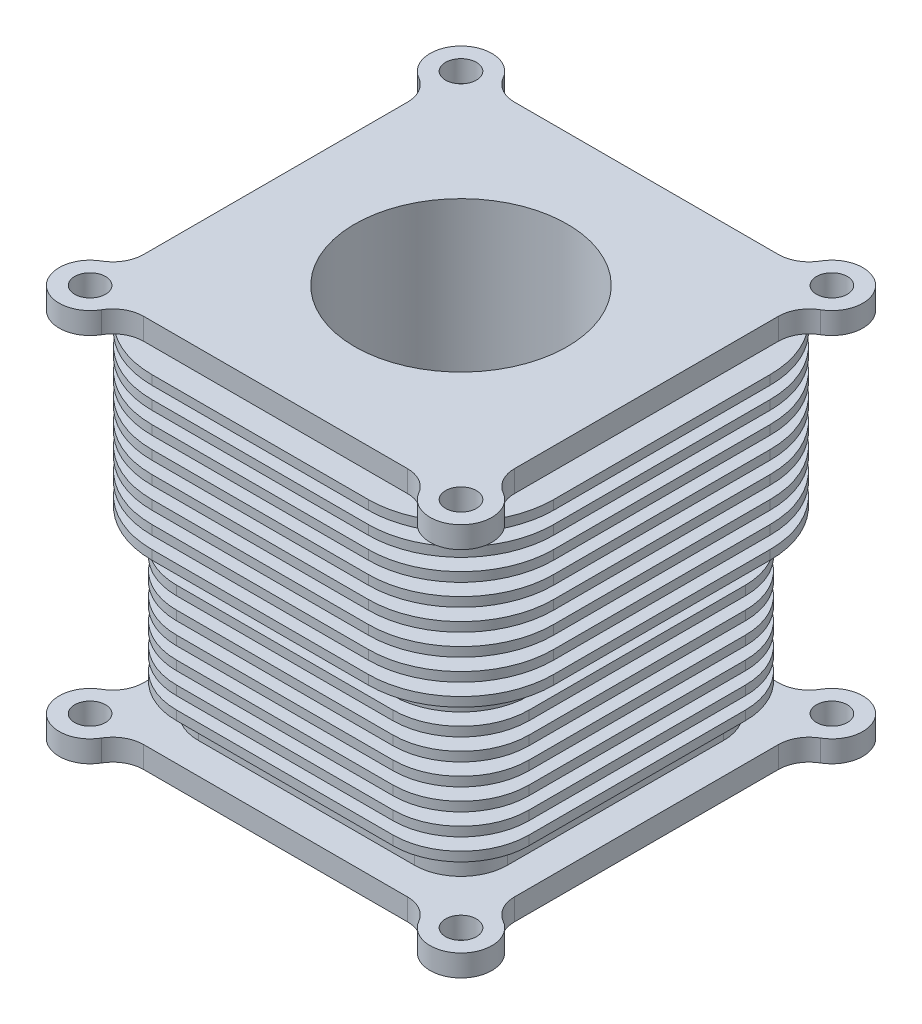
SolidWorks part; units mm, degrees
ref_plane "Front Plane" through (0, 0, 0) normal (0, 0, 1) x (1, 0, 0)
ref_plane "Top Plane" through (0, 0, 0) normal (0, 1, 0) x (1, 0, 0)
ref_plane "Right Plane" through (0, 0, 0) normal (1, 0, 0) x (0, 0, -1)
sketch "Sketch2" plane through (0, 0, 0) normal (0, 1, 0) x (1, 0, 0)
  line L1 (-63.5, 76.2) -> (63.5, 76.2)
  line L2 (-76.2, 63.5) -> (-76.2, -63.5)
  line L3 (-63.5, -76.2) -> (63.5, -76.2)
  line L4 (76.2, 63.5) -> (76.2, -63.5)
  line L5 (-76.2, 76.2) -> (76.2, -76.2) construction
  line L6 (-76.2, -76.2) -> (76.2, 76.2) construction
  arc A0 (-63.5, 76.2) -> (-76.2, 63.5) centre (-76.2, 76.2) ccw
  arc A1 (76.2, 63.5) -> (63.5, 76.2) centre (76.2, 76.2) ccw
  arc A2 (63.5, -76.2) -> (76.2, -63.5) centre (76.2, -76.2) ccw
  arc A3 (-76.2, -63.5) -> (-63.5, -76.2) centre (-76.2, -76.2) ccw
  point P0 (0, 0)
  dimension "D2" = 25.4
  dimension "D1" = 152.4
extrude "Boss-Extrude1" add sketch "Sketch2" along normal blind 8.89
fillet "Fillet1" radius 12.7 8 edges at (-63.5, 4.445, -76.2) (63.5, 4.445, -76.2) (76.2, 4.445, -63.5) (-76.2, 4.445, 63.5) (-76.2, 4.445, -63.5) (76.2, 4.445, 63.5) (63.5, 4.445, 76.2) (-63.5, 4.445, 76.2)
sketch "Sketch3" plane through (0, 8.89, 0) normal (0, 1, 0) x (1, 0, 0)
  line L1 (-63.5, 63.5) -> (63.5, 63.5)
  line L2 (-63.5, 63.5) -> (-63.5, -63.5)
  line L3 (-63.5, -63.5) -> (63.5, -63.5)
  line L4 (63.5, 63.5) -> (63.5, -63.5)
  line L5 (-63.5, 63.5) -> (63.5, -63.5) construction
  line L6 (-63.5, -63.5) -> (63.5, 63.5) construction
  point P0 (0, 0)
  dimension "D1" = 127
extrude "Boss-Extrude2" add sketch "Sketch3" along normal blind 152.4
fillet "Fillet2" radius 19.05 4 edges at (-63.5, 85.09, 63.5) (-63.5, 85.09, -63.5) (63.5, 85.09, -63.5) (63.5, 85.09, 63.5)
sketch "Sketch6" plane through (0, 161.29, 0) normal (0, 1, 0) x (1, 0, 0)
  line L8 (-82.55, 44.45) -> (-82.55, -44.45)
  line L9 (-44.45, -82.55) -> (44.45, -82.55)
  line L10 (82.55, -44.45) -> (82.55, 44.45)
  line L11 (44.45, 82.55) -> (-44.45, 82.55)
  line L12 (-82.55, 44.45) -> (-82.55, -44.45)
  line L13 (-44.45, -82.55) -> (44.45, -82.55)
  line L14 (82.55, -44.45) -> (82.55, 44.45)
  line L15 (44.45, 82.55) -> (-44.45, 82.55)
  arc A8 (-82.55, -44.45) -> (-44.45, -82.55) centre (-44.45, -44.45) ccw
  arc A9 (44.45, -82.55) -> (82.55, -44.45) centre (44.45, -44.45) ccw
  arc A10 (82.55, 44.45) -> (44.45, 82.55) centre (44.45, 44.45) ccw
  arc A11 (-44.45, 82.55) -> (-82.55, 44.45) centre (-44.45, 44.45) ccw
  arc A12 (-82.55, -44.45) -> (-44.45, -82.55) centre (-44.45, -44.45) ccw
  arc A13 (44.45, -82.55) -> (82.55, -44.45) centre (44.45, -44.45) ccw
  arc A14 (82.55, 44.45) -> (44.45, 82.55) centre (44.45, 44.45) ccw
  arc A15 (-44.45, 82.55) -> (-82.55, 44.45) centre (-44.45, 44.45) ccw
  dimension "D1" = 19.05
extrude "Boss-Extrude4" add sketch "Sketch6" against normal blind 3.81 from offset 12.7 offset against normal yes
pattern_linear "LPattern1" count 8 spacing 8.89 along (0, -1, 0) of "Boss-Extrude4"
ref_plane "Plane2" through (0, 80.645, 0) normal (0, 1, 0) x (1, 0, 0)
mirror "Mirror1" about plane through (0, 80.645, 0) normal (0, 1, 0) of "Fillet1", "Boss-Extrude1"
ref_plane "Plane3" through (0, 77.47, 0) normal (0, 1, 0) x (1, 0, 0)
sketch "Sketch8" plane through (0, 77.47, 0) normal (0, 1, 0) x (1, 0, 0)
  line L0 (-63.5, 44.45) -> (-63.5, -44.45) construction
  line L1 (44.45, 63.5) -> (-44.45, 63.5) construction
  line L2 (63.5, -44.45) -> (63.5, 44.45) construction
  line L3 (-44.45, -63.5) -> (44.45, -63.5) construction
  line L4 (-63.5, 44.45) -> (-63.5, -44.45)
  line L5 (44.45, 63.5) -> (-44.45, 63.5)
  line L6 (63.5, -44.45) -> (63.5, 44.45)
  line L7 (-44.45, -63.5) -> (44.45, -63.5)
  line L8 (72.39, -44.45) -> (72.39, 44.45)
  line L9 (44.45, 72.39) -> (-44.45, 72.39)
  line L10 (-72.39, 44.45) -> (-72.39, -44.45)
  line L11 (-44.45, -72.39) -> (44.45, -72.39)
  arc A0 (-63.5, -44.45) -> (-44.45, -63.5) centre (-44.45, -44.45) ccw construction
  arc A1 (-44.45, 63.5) -> (-63.5, 44.45) centre (-44.45, 44.45) ccw construction
  arc A2 (63.5, 44.45) -> (44.45, 63.5) centre (44.45, 44.45) ccw construction
  arc A3 (44.45, -63.5) -> (63.5, -44.45) centre (44.45, -44.45) ccw construction
  arc A4 (-63.5, -44.45) -> (-44.45, -63.5) centre (-44.45, -44.45) ccw
  arc A5 (-44.45, 63.5) -> (-63.5, 44.45) centre (-44.45, 44.45) ccw
  arc A6 (63.5, 44.45) -> (44.45, 63.5) centre (44.45, 44.45) ccw
  arc A7 (44.45, -63.5) -> (63.5, -44.45) centre (44.45, -44.45) ccw
  arc A8 (44.45, -72.39) -> (72.39, -44.45) centre (44.45, -44.45) ccw
  arc A9 (72.39, 44.45) -> (44.45, 72.39) centre (44.45, 44.45) ccw
  arc A10 (-44.45, 72.39) -> (-72.39, 44.45) centre (-44.45, 44.45) ccw
  arc A11 (-72.39, -44.45) -> (-44.45, -72.39) centre (-44.45, -44.45) ccw
  dimension "D1" = 8.89
extrude "Boss-Extrude5" add sketch "Sketch8" against normal blind 3.81
pattern_linear "LPattern2" count 7 spacing 8.89 along (0, -1, 0) of "Boss-Extrude5"
sketch "Sketch9" plane through (0, 161.29, 0) normal (0, 1, 0) x (1, 0, 0)
  circle A0 centre (0, 0) radius 43.6562
  dimension "D1" = 87.3125
extrude "Cut-Extrude1" cut sketch "Sketch9" against normal through all
sketch "Sketch10" plane through (0, 161.29, 0) normal (0, 1, 0) x (1, 0, 0)
  circle A0 centre (-76.2, 76.2) radius 6.35
  dimension "D1" = 12.7
extrude "Cut-Extrude2" cut sketch "Sketch10" against normal blind 12.7
ref_axis "Axis1" through (0, 0, 0) along (0, 1, 0)
pattern_circular "CirPattern1" count 4 over 360 about axis through (0, 0, 0) along (0, 1, 0) of "Cut-Extrude2"
mirror "Mirror3" about plane through (0, 80.645, 0) normal (0, 1, 0) of "CirPattern1"
